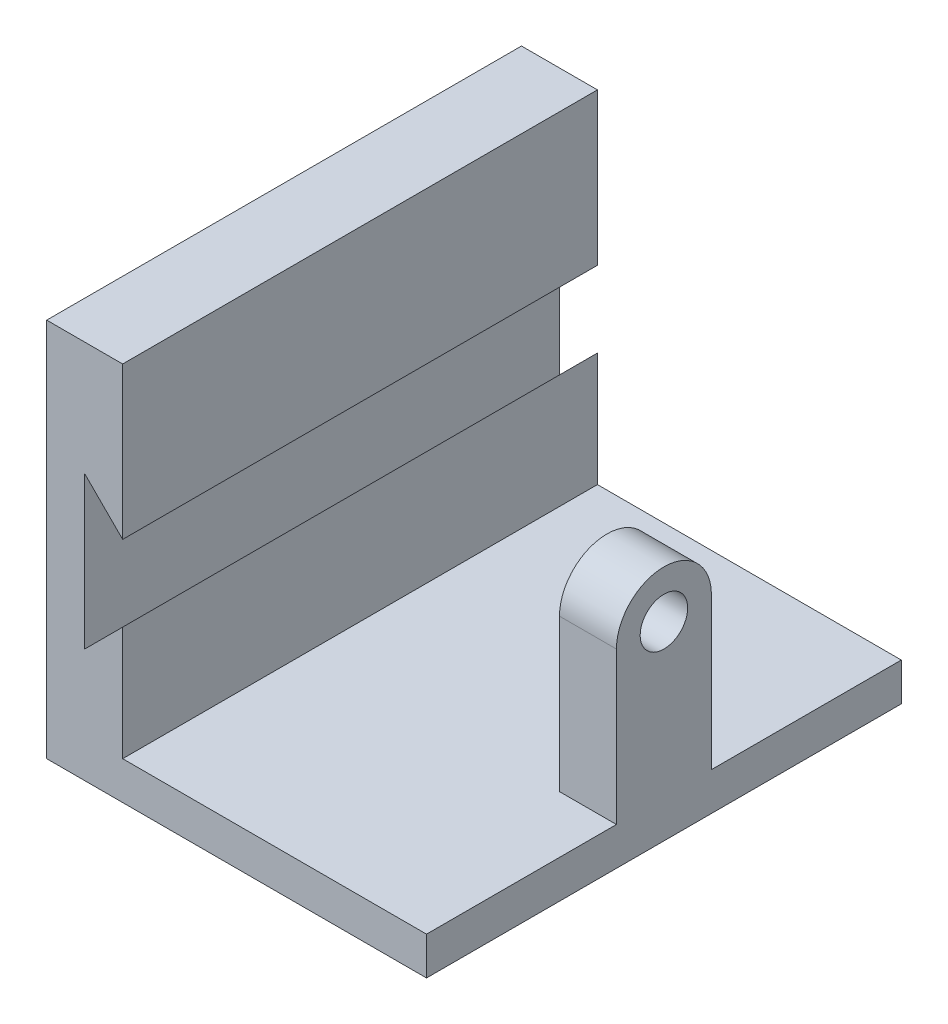
SolidWorks part; units mm, degrees
material "Plain Carbon Steel"
ref_plane "Front Plane" through (0, 0, 0) normal (0, 0, 1) x (1, 0, 0)
ref_plane "Top Plane" through (0, 0, 0) normal (0, 1, 0) x (1, 0, 0)
ref_plane "Right Plane" through (0, 0, 0) normal (1, 0, 0) x (0, 0, -1)
sketch "Sketch1" plane through (0, 0, 0) normal (0, 0, 1) x (1, 0, 0)
  line L0 (0, 0) -> (-200, 0)
  line L1 (-200, 0) -> (-200, 200)
  line L2 (-200, 200) -> (-160, 200)
  line L3 (-160, 200) -> (-160, 120)
  line L4 (-160, 20) -> (0, 20)
  line L5 (0, 20) -> (0, 0)
  line L6 (-160, 80) -> (-180, 60)
  line L7 (-180, 60) -> (-180, 140)
  line L8 (-180, 140) -> (-160, 120)
  line L9 (-160, 80) -> (-160, 20)
  line L10 (-160, 120) -> (-160, 80) construction
  point P10 (-180, 100)
  point P12 (-160, 100)
  dimension "D1" = 200
  dimension "D2" = 200
  dimension "D3" = 20
  dimension "D4" = 40
  dimension "D5" = 80
  dimension "D6" = 20
  dimension "D7" = 20
  dimension "D8" = 45
extrude "Boss-Extrude1" add sketch "Sketch1" along normal mid plane 250
sketch "Sketch2" plane through (0, 0, 0) normal (1, 0, 0) x (0, 0, -1)
  line L0 (0, 100) -> (0, 0) construction
  line L1 (-25, 100) -> (-25, 0)
  line L2 (-125, 0) -> (125, 0) construction
  line L3 (-25, 0) -> (0, 0)
  line L4 (0, 0) -> (25, 0)
  line L5 (25, 0) -> (25, 100)
  circle A0 centre (0, 100) radius 12.5
  arc A1 (25, 100) -> (-25, 100) centre (0, 100) ccw
  dimension "D1" = 25
  dimension "D2" = 25
  dimension "D3" = 100
extrude "Boss-Extrude2" add sketch "Sketch2" against normal blind 30
